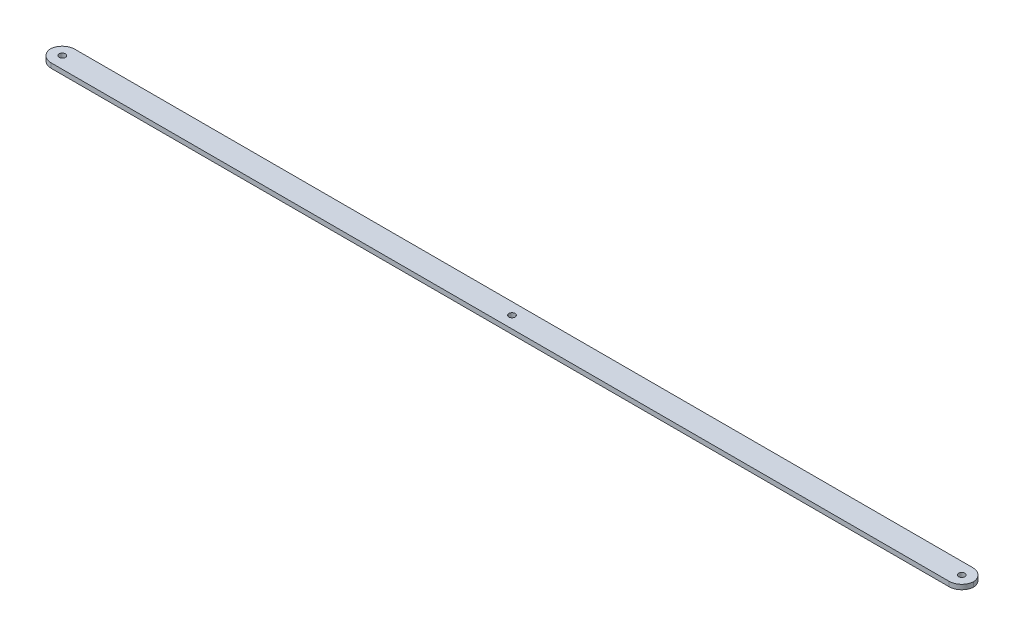
SolidWorks part; units mm, degrees
ref_plane "Front Plane" through (0, 0, 0) normal (0, 0, 1) x (1, 0, 0)
ref_plane "Top Plane" through (0, 0, 0) normal (0, 1, 0) x (1, 0, 0)
ref_plane "Right Plane" through (0, 0, 0) normal (1, 0, 0) x (0, 0, -1)
sketch "Sketch1" plane through (0, 0, 0) normal (0, 1, 0) x (1, 0, 0)
  line L0 (142.5, 7.5) -> (142.5, -7.5) construction
  line L1 (-150, -7.5) -> (150, -7.5)
  line L2 (-150, -7.5) -> (-150, 7.5)
  line L3 (-150, 7.5) -> (150, 7.5)
  line L4 (150, -7.5) -> (150, 7.5)
  line L5 (-150, -7.5) -> (150, 7.5) construction
  line L6 (-150, 7.5) -> (150, -7.5) construction
  line L7 (435, -7.5) -> (435, 7.5)
  line L8 (135, -7.5) -> (135, 7.5)
  line L9 (435, -7.5) -> (135, -7.5)
  line L10 (435, 7.5) -> (135, 7.5)
  circle A0 centre (-142.5, 0) radius 2
  circle A1 centre (142.5, 0) radius 2
  circle A2 centre (427.5, 0) radius 2
  point P0 (0, 0)
  dimension "D3" = 4
  dimension "D4" = 7.5
  dimension "D6" = 4
  dimension "D7" = 7.5
  dimension "D8" = 142.5
  dimension "D5" = 142.5
  dimension "D1" = 300
  dimension "D2" = 15
extrude "Boss-Extrude1" add sketch "Sketch1" along normal blind 3 contours L1 L8 L3 L2 A0 | L7 L10 L4 L9 A2 | L8 L1 L4 L3 A1 region at (-7.102, 0, 0) region at (135.2121, 0, 0) region at (292.102, 0, 0)
fillet "Fillet1" radius 8 4 edges at (-150, 1.5, 7.5) (-150, 1.5, -7.5) (435, 1.5, 7.5) (435, 1.5, -7.5)
